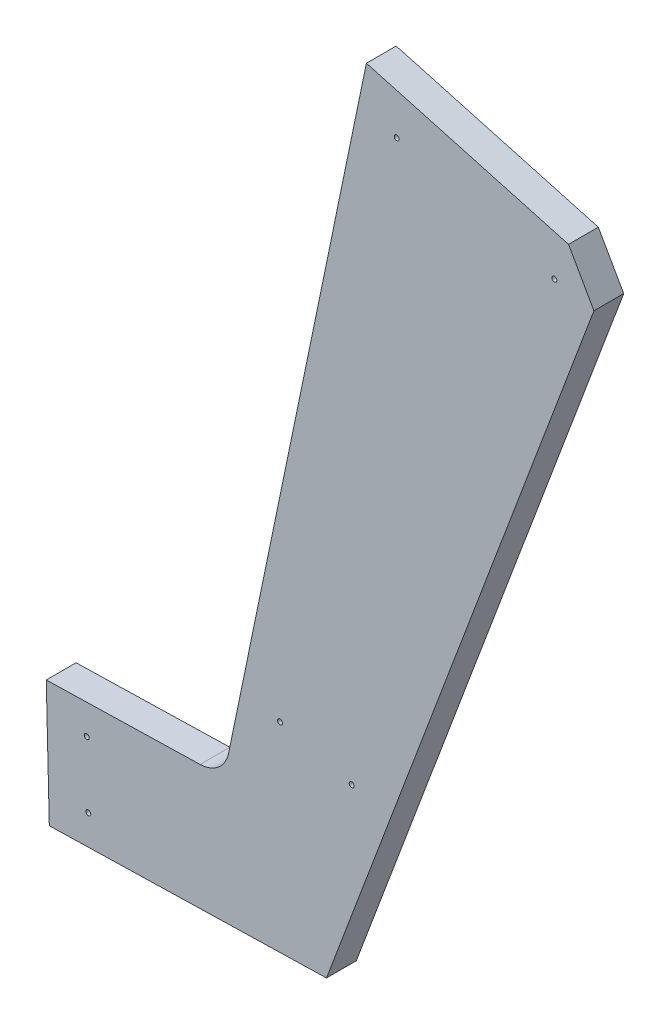
SolidWorks part; units mm, degrees
material "Beech"
ref_plane "Front Plane" through (0, 0, 0) normal (0, 0, 1) x (1, 0, 0)
ref_plane "Top Plane" through (0, 0, 0) normal (0, 1, 0) x (1, 0, 0)
ref_plane "Right Plane" through (0, 0, 0) normal (1, 0, 0) x (0, 0, -1)
sketch "Sketch1" plane through (0, 0, 0) normal (0, 0, 1) x (1, 0, 0)
  line L0 (-61.7531, -505.1337) -> (-59.8053, -584.9036)
  line L1 (-70.6552, -530.7587) -> (-61.1331, -530.5262) construction
  line L12 (272.1416, -96.993) -> (142.9339, -61.3062)
  line L13 (142.9339, -61.3062) -> (54.7807, -487.5464)
  line L14 (36.5905, -502.7325) -> (-61.7531, -505.1337)
  line L16 (-59.8053, -584.9036) -> (117.3871, -580.5771)
  line L17 (117.3871, -580.5771) -> (288.3946, -125.6501)
  line L37 (288.3946, -125.6501) -> (272.1416, -96.993)
  arc A0 (54.7807, -487.5464) -> (36.5905, -502.7325) centre (36.1255, -483.6882) cw
  dimension "D2" = 19.05
  dimension "D1" = 112
  dimension "D3" = 9.525
  dimension "D4" = 79.7937
  dimension "D5" = 435.6771
  dimension "D6" = 84.839
extrude "Boss-Extrude1" add sketch "Sketch1" along normal blind 19.05
hole_wizard "Hole2" positions "Sketch4" profile "Sketch5" legacy
sketch "Sketch4" plane through (295.8209, -105.8941, -19.05) normal (0, 0, -1) x (-0.3519, -0.9361, 0)
  line L0 (9.7688, 133.4475) -> (528.1685, 52.1167) construction
  line L5 (0.0093, 25.4) -> (517.3743, 25.4) construction
  line L8 (660.1216, 540.8653) -> (441.5979, 0) construction
  line L11 (698.7793, 525.2466) -> (486.5659, 0) construction
  line L15 (604.5365, 403.2872) -> (643.1942, 387.6685) construction
  line L17 (520.7568, 195.9254) -> (559.4145, 180.3066) construction
  line L19 (507.6737, 163.5435) -> (546.3314, 147.9247) construction
  point P17 (34.8618, 129.5107)
  point P19 (398.7112, 72.427)
  point P22 (25.4093, 25.4)
  point P24 (393.7093, 25.4)
  point P40 (604.5365, 403.2872)
  point P41 (643.1942, 387.6685)
  point P44 (520.7568, 195.9254)
  point P45 (559.4145, 180.3066)
  point P48 (507.6737, 163.5435)
  point P49 (546.3314, 147.9247)
sketch "Sketch5" plane through (-34.8779, -565.2393, -19.05) normal (1, 0, 0) x (0, 1, 0)
  line L0 (0, 0) -> (0, 40.64)
  line L1 (0, 40.64) -> (1.5875, 39.6861)
  line L2 (1.5875, 39.6861) -> (1.5875, 4.0177)
  line L3 (1.5875, 4.0177) -> (5.08, 0)
  line L4 (5.08, 0) -> (0, 0)
  line L5 (0, -14.3089) -> (0, 102.4216) construction
  line L6 (0, 40.64) -> (-1.5875, 39.6861) construction
  line L7 (-1.5875, 4.0177) -> (-5.08, 0) construction
  dimension "Diameter" = 3.175
  dimension "Depth" = 40.64
  dimension "C-Sink Diameter" = 10.16
  dimension "C-Sink Angle" = 82
  dimension "Drill Angle" = 118
